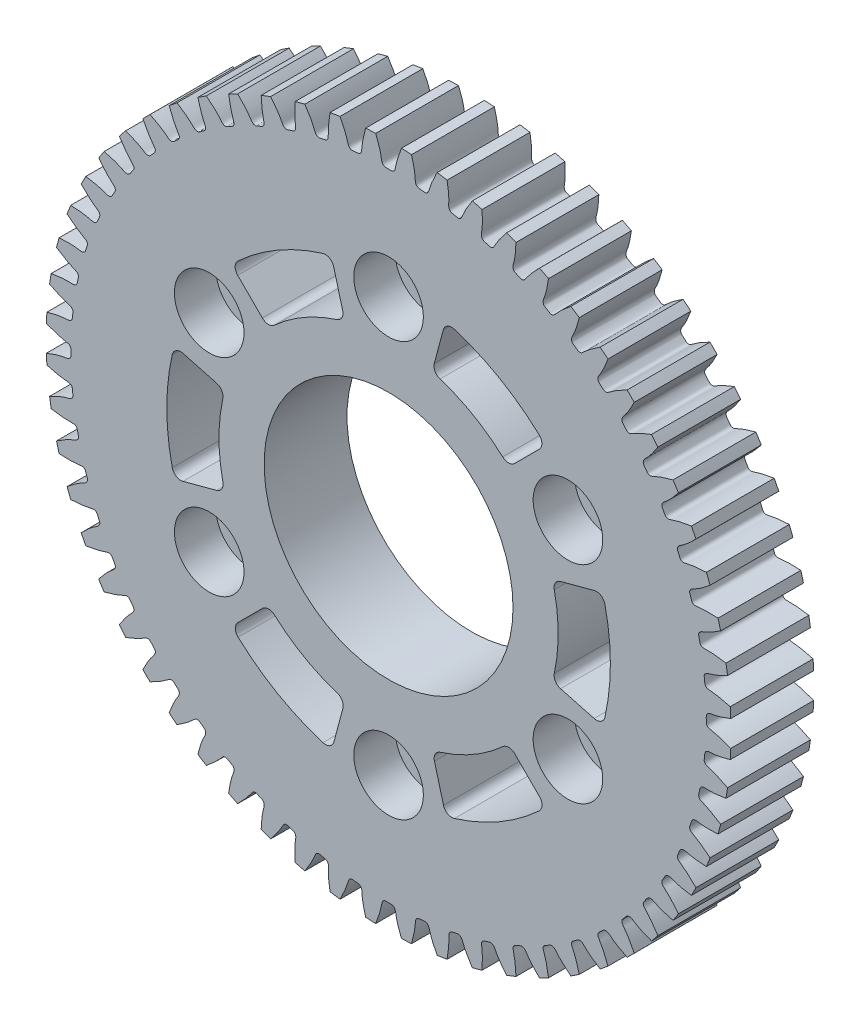
SolidWorks part; units mm, degrees
ref_plane "Front Plane" through (0, 0, 0) normal (0, 0, 1) x (1, 0, 0)
ref_plane "Top Plane" through (0, 0, 0) normal (0, 1, 0) x (1, 0, 0)
ref_plane "Right Plane" through (0, 0, 0) normal (1, 0, 0) x (0, 0, -1)
ref_axis "Axis1" through (0, 0, 0) along (0, 0, 1)
sketch "Sketch1" plane through (0, 0, 0) normal (0, 0, 1) x (1, 0, 0)
  arc A0 (38.9718, 5.5854) -> (38.7904, 6.7309) centre (0, 0) ccw
  arc A1 (38.1745, 9.6285) -> (37.8743, 10.7487) centre (0, 0) ccw
  arc A2 (36.9589, 13.566) -> (36.5433, 14.6488) centre (0, 0) ccw
  arc A3 (35.3384, 17.355) -> (34.8118, 18.3884) centre (0, 0) ccw
  arc A4 (33.3307, 20.9538) -> (32.699, 21.9265) centre (0, 0) ccw
  arc A5 (30.9579, 24.323) -> (30.228, 25.2243) centre (0, 0) ccw
  arc A6 (28.2458, 27.4257) -> (27.4257, 28.2458) centre (0, 0) ccw
  arc A7 (25.2243, 30.228) -> (24.323, 30.9579) centre (0, 0) ccw
  arc A8 (21.9265, 32.699) -> (20.9538, 33.3307) centre (0, 0) ccw
  arc A9 (18.3884, 34.8118) -> (17.355, 35.3384) centre (0, 0) ccw
  arc A10 (14.6488, 36.5433) -> (13.566, 36.9589) centre (0, 0) ccw
  arc A11 (10.7487, 37.8743) -> (9.6285, 38.1745) centre (0, 0) ccw
  arc A12 (6.7309, 38.7904) -> (5.5854, 38.9718) centre (0, 0) ccw
  arc A13 (2.6394, 39.2814) -> (1.4811, 39.3421) centre (0, 0) ccw
  arc A14 (-1.4811, 39.3421) -> (-2.6394, 39.2814) centre (0, 0) ccw
  arc A15 (-5.5854, 38.9718) -> (-6.7309, 38.7904) centre (0, 0) ccw
  arc A16 (-9.6285, 38.1745) -> (-10.7487, 37.8743) centre (0, 0) ccw
  arc A17 (-13.566, 36.9589) -> (-14.6488, 36.5433) centre (0, 0) ccw
  arc A18 (-17.355, 35.3384) -> (-18.3884, 34.8118) centre (0, 0) ccw
  arc A19 (-20.9538, 33.3307) -> (-21.9265, 32.699) centre (0, 0) ccw
  arc A20 (-24.323, 30.9579) -> (-25.2243, 30.228) centre (0, 0) ccw
  arc A21 (-27.4257, 28.2458) -> (-28.2458, 27.4257) centre (0, 0) ccw
  arc A22 (-30.228, 25.2243) -> (-30.9579, 24.323) centre (0, 0) ccw
  arc A23 (-32.699, 21.9265) -> (-33.3307, 20.9538) centre (0, 0) ccw
  arc A24 (-34.8118, 18.3884) -> (-35.3384, 17.355) centre (0, 0) ccw
  arc A25 (-36.5433, 14.6488) -> (-36.9589, 13.566) centre (0, 0) ccw
  arc A26 (-37.8743, 10.7487) -> (-38.1745, 9.6285) centre (0, 0) ccw
  arc A27 (-38.7904, 6.7309) -> (-38.9718, 5.5854) centre (0, 0) ccw
  arc A28 (-39.2814, 2.6394) -> (-39.3421, 1.4811) centre (0, 0) ccw
  arc A29 (-39.3421, -1.4811) -> (-39.2814, -2.6394) centre (0, 0) ccw
  arc A30 (-38.9718, -5.5854) -> (-38.7904, -6.7309) centre (0, 0) ccw
  arc A31 (-38.1745, -9.6285) -> (-37.8743, -10.7487) centre (0, 0) ccw
  arc A32 (-36.9589, -13.566) -> (-36.5433, -14.6488) centre (0, 0) ccw
  arc A33 (-35.3384, -17.355) -> (-34.8118, -18.3884) centre (0, 0) ccw
  arc A34 (-33.3307, -20.9538) -> (-32.699, -21.9265) centre (0, 0) ccw
  arc A35 (-30.9579, -24.323) -> (-30.228, -25.2243) centre (0, 0) ccw
  arc A36 (-28.2458, -27.4257) -> (-27.4257, -28.2458) centre (0, 0) ccw
  arc A37 (-25.2243, -30.228) -> (-24.323, -30.9579) centre (0, 0) ccw
  arc A38 (-21.9265, -32.699) -> (-20.9538, -33.3307) centre (0, 0) ccw
  arc A39 (-18.3884, -34.8118) -> (-17.355, -35.3384) centre (0, 0) ccw
  arc A40 (-14.6488, -36.5433) -> (-13.566, -36.9589) centre (0, 0) ccw
  arc A41 (-10.7487, -37.8743) -> (-9.6285, -38.1745) centre (0, 0) ccw
  arc A42 (-6.7309, -38.7904) -> (-5.5854, -38.9718) centre (0, 0) ccw
  arc A43 (-2.6394, -39.2814) -> (-1.4811, -39.3421) centre (0, 0) ccw
  arc A44 (1.4811, -39.3421) -> (2.6394, -39.2814) centre (0, 0) ccw
  arc A45 (5.5854, -38.9718) -> (6.7309, -38.7904) centre (0, 0) ccw
  arc A46 (9.6285, -38.1745) -> (10.7487, -37.8743) centre (0, 0) ccw
  arc A47 (13.566, -36.9589) -> (14.6488, -36.5433) centre (0, 0) ccw
  arc A48 (17.355, -35.3384) -> (18.3884, -34.8118) centre (0, 0) ccw
  arc A49 (20.9538, -33.3307) -> (21.9265, -32.699) centre (0, 0) ccw
  arc A50 (24.323, -30.9579) -> (25.2243, -30.228) centre (0, 0) ccw
  arc A51 (27.4257, -28.2458) -> (28.2458, -27.4257) centre (0, 0) ccw
  arc A52 (30.228, -25.2243) -> (30.9579, -24.323) centre (0, 0) ccw
  arc A53 (32.699, -21.9265) -> (33.3307, -20.9538) centre (0, 0) ccw
  arc A54 (34.8118, -18.3884) -> (35.3384, -17.355) centre (0, 0) ccw
  arc A55 (36.5433, -14.6488) -> (36.9589, -13.566) centre (0, 0) ccw
  arc A56 (37.8743, -10.7487) -> (38.1745, -9.6285) centre (0, 0) ccw
  arc A57 (38.7904, -6.7309) -> (38.9718, -5.5854) centre (0, 0) ccw
  arc A58 (39.2814, -2.6394) -> (39.3421, -1.4811) centre (0, 0) ccw
  arc A59 (39.3421, 1.4811) -> (39.2814, 2.6394) centre (0, 0) ccw
  spline S0 degree 3 number of poles 79 (38.1745, 9.6285) -> (38.7904, 6.7309)
  spline S1 degree 3 number of poles 79 (36.9589, 13.566) -> (37.8743, 10.7487)
  spline S2 degree 3 number of poles 79 (35.3384, 17.355) -> (36.5433, 14.6488)
  spline S3 degree 3 number of poles 79 (33.3307, 20.9538) -> (34.8118, 18.3884)
  spline S4 degree 3 number of poles 79 (30.9579, 24.323) -> (32.699, 21.9265)
  spline S5 degree 3 number of poles 79 (28.2458, 27.4257) -> (30.228, 25.2243)
  spline S6 degree 3 number of poles 79 (25.2243, 30.228) -> (27.4257, 28.2458)
  spline S7 degree 3 number of poles 79 (21.9265, 32.699) -> (24.323, 30.9579)
  spline S8 degree 3 number of poles 79 (18.3884, 34.8118) -> (20.9538, 33.3307)
  spline S9 degree 3 number of poles 79 (14.6488, 36.5433) -> (17.355, 35.3384)
  spline S10 degree 3 number of poles 79 (10.7487, 37.8743) -> (13.566, 36.9589)
  spline S11 degree 3 number of poles 79 (6.7309, 38.7904) -> (9.6285, 38.1745)
  spline S12 degree 3 number of poles 79 (2.6394, 39.2814) -> (5.5854, 38.9718)
  spline S13 degree 3 number of poles 79 (-1.4811, 39.3421) -> (1.4811, 39.3421)
  spline S14 degree 3 number of poles 79 (-5.5854, 38.9718) -> (-2.6394, 39.2814)
  spline S15 degree 3 number of poles 79 (-9.6285, 38.1745) -> (-6.7309, 38.7904)
  spline S16 degree 3 number of poles 79 (-13.566, 36.9589) -> (-10.7487, 37.8743)
  spline S17 degree 3 number of poles 79 (-17.355, 35.3384) -> (-14.6488, 36.5433)
  spline S18 degree 3 number of poles 79 (-20.9538, 33.3307) -> (-18.3884, 34.8118)
  spline S19 degree 3 number of poles 79 (-24.323, 30.9579) -> (-21.9265, 32.699)
  spline S20 degree 3 number of poles 79 (-27.4257, 28.2458) -> (-25.2243, 30.228)
  spline S21 degree 3 number of poles 79 (-30.228, 25.2243) -> (-28.2458, 27.4257)
  spline S22 degree 3 number of poles 79 (-32.699, 21.9265) -> (-30.9579, 24.323)
  spline S23 degree 3 number of poles 79 (-34.8118, 18.3884) -> (-33.3307, 20.9538)
  spline S24 degree 3 number of poles 79 (-36.5433, 14.6488) -> (-35.3384, 17.355)
  spline S25 degree 3 number of poles 79 (-37.8743, 10.7487) -> (-36.9589, 13.566)
  spline S26 degree 3 number of poles 79 (-38.7904, 6.7309) -> (-38.1745, 9.6285)
  spline S27 degree 3 number of poles 79 (-39.2814, 2.6394) -> (-38.9718, 5.5854)
  spline S28 degree 3 number of poles 79 (-39.3421, -1.4811) -> (-39.3421, 1.4811)
  spline S29 degree 3 number of poles 79 (-38.9718, -5.5854) -> (-39.2814, -2.6394)
  spline S30 degree 3 number of poles 79 (-38.1745, -9.6285) -> (-38.7904, -6.7309)
  spline S31 degree 3 number of poles 79 (-36.9589, -13.566) -> (-37.8743, -10.7487)
  spline S32 degree 3 number of poles 79 (-35.3384, -17.355) -> (-36.5433, -14.6488)
  spline S33 degree 3 number of poles 79 (-33.3307, -20.9538) -> (-34.8118, -18.3884)
  spline S34 degree 3 number of poles 79 (-30.9579, -24.323) -> (-32.699, -21.9265)
  spline S35 degree 3 number of poles 79 (-28.2458, -27.4257) -> (-30.228, -25.2243)
  spline S36 degree 3 number of poles 79 (-25.2243, -30.228) -> (-27.4257, -28.2458)
  spline S37 degree 3 number of poles 79 (-21.9265, -32.699) -> (-24.323, -30.9579)
  spline S38 degree 3 number of poles 79 (-18.3884, -34.8118) -> (-20.9538, -33.3307)
  spline S39 degree 3 number of poles 79 (-14.6488, -36.5433) -> (-17.355, -35.3384)
  spline S40 degree 3 number of poles 79 (-10.7487, -37.8743) -> (-13.566, -36.9589)
  spline S41 degree 3 number of poles 79 (-6.7309, -38.7904) -> (-9.6285, -38.1745)
  spline S42 degree 3 number of poles 79 (-2.6394, -39.2814) -> (-5.5854, -38.9718)
  spline S43 degree 3 number of poles 79 (1.4811, -39.3421) -> (-1.4811, -39.3421)
  spline S44 degree 3 number of poles 79 (5.5854, -38.9718) -> (2.6394, -39.2814)
  spline S45 degree 3 number of poles 79 (9.6285, -38.1745) -> (6.7309, -38.7904)
  spline S46 degree 3 number of poles 79 (13.566, -36.9589) -> (10.7487, -37.8743)
  spline S47 degree 3 number of poles 79 (17.355, -35.3384) -> (14.6488, -36.5433)
  spline S48 degree 3 number of poles 79 (20.9538, -33.3307) -> (18.3884, -34.8118)
  spline S49 degree 3 number of poles 79 (24.323, -30.9579) -> (21.9265, -32.699)
  spline S50 degree 3 number of poles 79 (27.4257, -28.2458) -> (25.2243, -30.228)
  spline S51 degree 3 number of poles 79 (30.228, -25.2243) -> (28.2458, -27.4257)
  spline S52 degree 3 number of poles 79 (32.699, -21.9265) -> (30.9579, -24.323)
  spline S53 degree 3 number of poles 79 (34.8118, -18.3884) -> (33.3307, -20.9538)
  spline S54 degree 3 number of poles 79 (36.5433, -14.6488) -> (35.3384, -17.355)
  spline S55 degree 3 number of poles 79 (37.8743, -10.7487) -> (36.9589, -13.566)
  spline S56 degree 3 number of poles 79 (38.7904, -6.7309) -> (38.1745, -9.6285)
  spline S57 degree 3 number of poles 79 (39.2814, -2.6394) -> (38.9718, -5.5854)
  spline S58 degree 3 number of poles 79 (39.3421, 1.4811) -> (39.3421, -1.4811)
  spline S59 degree 3 number of poles 79 (38.9718, 5.5854) -> (39.2814, 2.6394)
extrude "Boss-Extrude1" add sketch "Sketch1" against normal blind 9.525
sketch "Sketch2" plane through (0, 0, 0) normal (0, 0, 1) x (1, 0, 0)
  line L0 (6.2872, 23.6606) -> (5.251, 19.7934)
  line L1 (14.4973, 14.4613) -> (17.3284, 17.2924)
  arc A0 (5.251, 19.7934) -> (5.9137, 18.5817) centre (6.217, 19.5346) ccw
  arc A1 (5.9137, 18.5817) -> (13.1175, 14.4285) centre (0, 0) cw
  arc A2 (13.1175, 14.4285) -> (14.4973, 14.4613) centre (13.7902, 15.1684) ccw
  arc A3 (17.3284, 17.2924) -> (17.2997, 18.7342) centre (16.6213, 17.9996) ccw
  arc A4 (17.2997, 18.7342) -> (7.5492, 24.3569) centre (0, 0) ccw
  arc A5 (7.5492, 24.3569) -> (6.2872, 23.6606) centre (7.2532, 23.4017) ccw
extrude "Cut-Extrude1" cut sketch "Sketch2" against normal through all
sketch "Sketch3" plane through (0, 0, 0) normal (0, 0, 1) x (1, 0, 0)
  circle A0 centre (0, 23.8125) radius 4
extrude "Cut-Extrude2" cut sketch "Sketch3" against normal blind 4.7625
sketch "Sketch4" plane through (0, 0, -9.525) normal (0, 0, -1) x (-1, 0, 0)
  circle A0 centre (-20.6222, -11.9063) radius 2.15
extrude "Cut-Extrude3" cut sketch "Sketch4" against normal through all
sketch "Sketch5" plane through (0, 0, -9.525) normal (0, 0, -1) x (-1, 0, 0)
  circle A0 centre (0, 0) radius 14.3065
extrude "Cut-Extrude4" cut sketch "Sketch5" against normal through all
pattern_circular "CirPattern1" count 6 every 60 about axis through (0, 0, 0) along (0, 0, 1) of "Cut-Extrude1", "Cut-Extrude2", "Cut-Extrude3"
